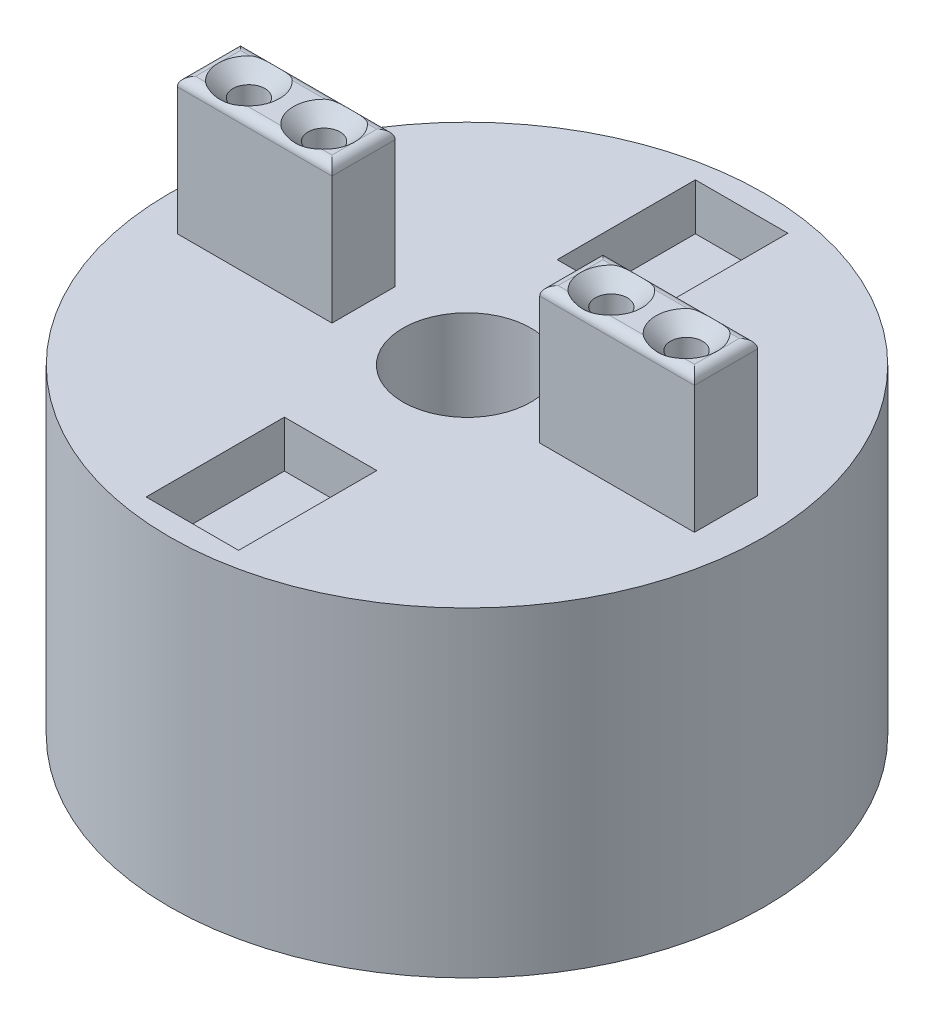
SolidWorks part; units mm, degrees
ref_plane "Front Plane" through (0, 0, 0) normal (0, 0, 1) x (1, 0, 0)
ref_plane "Top Plane" through (0, 0, 0) normal (0, 1, 0) x (1, 0, 0)
ref_plane "Right Plane" through (0, 0, 0) normal (1, 0, 0) x (0, 0, -1)
sketch "Sketch1" plane through (0, 0, 0) normal (0, 1, 0) x (1, 0, 0)
  circle A0 centre (0, 0) radius 32.5
  dimension "D1" = 65
extrude "Boss-Extrude1" add sketch "Sketch1" along normal blind 35 contours A0
sketch "Sketch2" plane through (0, 35, 0) normal (0, 1, 0) x (1, 0, 0)
  line L1 (-5.05, 30) -> (5.05, 30)
  line L2 (-5.05, 30) -> (-5.05, 14.9)
  line L3 (-5.05, 14.9) -> (5.05, 14.9)
  line L4 (5.05, 30) -> (5.05, 14.9)
  line L5 (5.05, -30) -> (5.05, -14.9)
  line L6 (-5.05, -14.9) -> (5.05, -14.9)
  line L7 (-5.05, -30) -> (-5.05, -14.9)
  line L8 (-5.05, -30) -> (5.05, -30)
  point P0 (0, 22.45)
  point P5 (0, -22.45)
  dimension "D3" = 0
extrude "Cut-Extrude1" cut sketch "Sketch2" against normal blind 5.1
sketch "Sketch3" plane through (0, 35, 0) normal (0, 1, 0) x (1, 0, 0)
  circle A0 centre (0, 0) radius 7
extrude "Cut-Extrude2" cut sketch "Sketch3" against normal through all
sketch "Sketch4" plane through (0, 35, 0) normal (0, 1, 0) x (1, 0, 0)
  line L0 (0, 0) -> (0, 11.6634) construction
  line L1 (11.3462, -3.4) -> (28.2462, -3.4)
  line L2 (11.3462, -3.4) -> (11.3462, 3.5)
  line L3 (11.3462, 3.5) -> (28.2462, 3.5)
  line L4 (28.2462, -3.4) -> (28.2462, 3.5)
  line L9 (-28.2462, -3.4) -> (-28.2462, 3.5)
  line L10 (-11.3462, 3.5) -> (-28.2462, 3.5)
  line L11 (-11.3462, -3.4) -> (-11.3462, 3.5)
  line L12 (-11.3462, -3.4) -> (-28.2462, -3.4)
  point P0 (19.7462, 0)
  point P9 (-19.7462, 0)
  dimension "D1" = 16.9
  dimension "D2" = 6.9
  dimension "D3" = 0
extrude "Boss-Extrude2" add sketch "Sketch4" along normal blind 14.9
fillet "Fillet2" radius 1 8 edges at (19.7962, 49.9, 3.4) (11.3462, 49.9, -0.05) (19.7962, 49.9, -3.5) (28.2462, 49.9, -0.05) (-28.2462, 49.9, -0.05) (-19.7962, 49.9, -3.5) (-11.3462, 49.9, -0.05) (-19.7962, 49.9, 3.4)
sketch "Sketch5" plane through (0, 49.9, 0) normal (0, 1, 0) x (1, 0, 0)
  line L0 (0, 0) -> (0, 3.7315) construction
  circle A0 centre (23.9018, 0.0785) radius 1.75
  circle A1 centre (15.6906, 0.0785) radius 1.75
  circle A2 centre (-15.6906, 0.0785) radius 1.75
  circle A3 centre (-23.9018, 0.0785) radius 1.75
extrude "Cut-Extrude3" cut sketch "Sketch5" against normal blind 30
chamfer "Chamfer1" distance 1.6 angle 45 4 edges at (15.6906, 49.9, -1.8285) (23.9018, 49.9, 1.6715) (-15.6906, 49.9, 1.6715) (-23.9018, 49.9, -1.8285)
